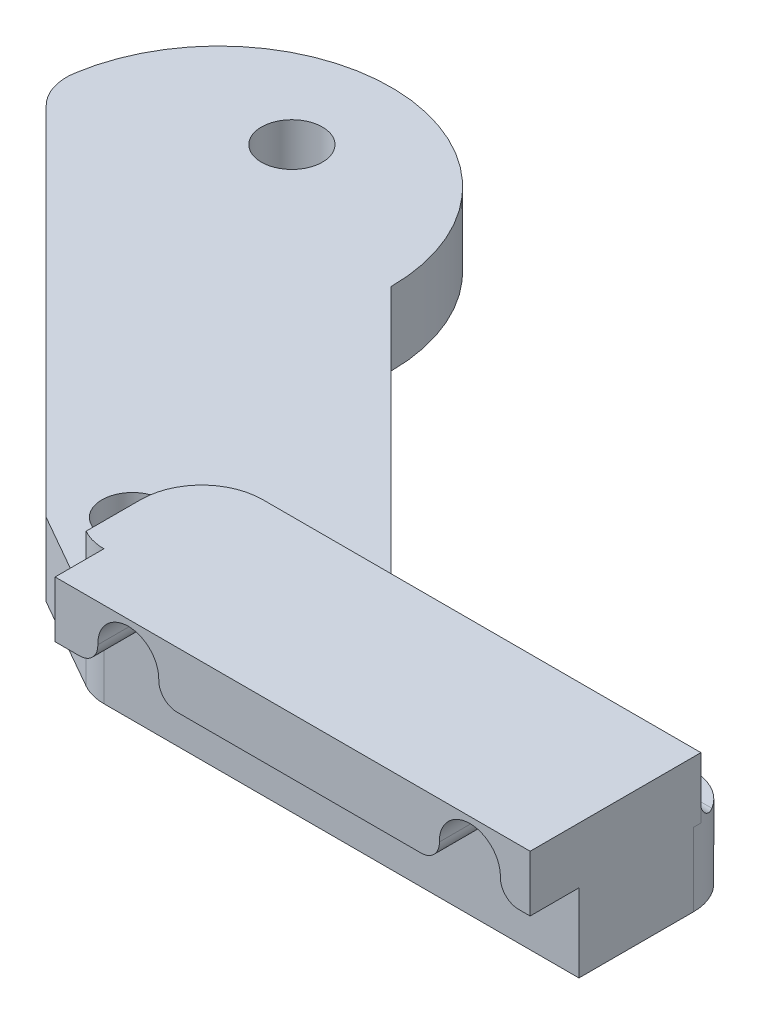
SolidWorks part; units mm, degrees
ref_plane "Front Plane" through (0, 0, 0) normal (0, 0, 1) x (1, 0, 0)
ref_plane "Top Plane" through (0, 0, 0) normal (0, 1, 0) x (1, 0, 0)
ref_plane "Right Plane" through (0, 0, 0) normal (1, 0, 0) x (0, 0, -1)
sketch "Sketch1" plane through (0, 0, 0) normal (0, 1, 0) x (1, 0, 0)
  line L0 (0, 6.35) -> (12.3665, 6.35)
  line L1 (12.3665, 6.35) -> (57.15, 6.35)
  line L2 (6.35, 0) -> (6.35, -10.668)
  line L3 (6.35, -10.668) -> (57.15, -10.668)
  line L4 (57.15, 6.35) -> (57.15, -10.668)
  line L5 (20.5908, 6.35) -> (-7.3492, 34.29)
  line L6 (-4.4901, -4.4901) -> (-43.2703, 34.29)
  line L7 (-4.4901, -4.4901) -> (6.35, -10.668)
  circle A0 centre (0, 0) radius 3.175
  arc A1 (0, 6.35) -> (6.35, 0) centre (0, 0) ccw
  arc A2 (-43.2703, 34.29) -> (-7.3492, 34.29) centre (-25.3097, 34.29) cw
  point P13 (-4.4901, -4.4901)
  dimension "D1" = 12.7
  dimension "D2" = 6.35
  dimension "D3" = 6.35
  dimension "D4" = 50.8
  dimension "D5" = 17.018
  dimension "D6" = 45
  dimension "D7" = 25.4
  dimension "D8" = 27.94
extrude "Boss-Extrude1" add sketch "Sketch1" along normal mid plane 7.62 contours A2 L6 A1 L0 L1 L5 | L0 A1 L2 L3 L4 L1 A0 | A1 L7 L2 region at (-15.7867, 0, -26.7963) region at (28.4111, 0, 1.8819) region at (4.1931, 0, 6.7992)
fillet "Fillet1" radius 5.08 4 edges at (57.15, 0, -6.35) (20.5908, 0, -6.35) (6.35, 0, 10.668) (-43.2703, 0, -34.29)
sketch "Sketch3" plane through (0, 3.81, 0) normal (0, 1, 0) x (1, 0, 0)
  circle A0 centre (-25.3097, 41.91) radius 3.175
  arc A1 (-7.3492, 34.29) -> (-43.0622, 37.016) centre (-25.3097, 34.29) ccw construction
  arc A2 (-7.3492, 34.29) -> (-43.0622, 37.016) centre (-25.3097, 34.29) ccw
  dimension "D2" = 6.35
  dimension "D1" = 7.62
extrude "Cut-Extrude2" cut sketch "Sketch3" against normal through all contours A0 region at (-25.3097, 3.81, -41.91)
sketch "Sketch4" plane through (0, 3.81, 0) normal (0, 1, 0) x (1, 0, 0)
  line L1 (57.15, -10.668) -> (7.6959, -10.668)
  line L2 (57.15, -10.668) -> (57.15, 2.032)
  line L3 (57.15, 2.032) -> (11.5306, 2.032)
  line L4 (5.1806, -10.0016) -> (5.1806, -4.318)
  arc A0 (5.1806, -10.0016) -> (7.6959, -10.668) centre (7.6959, -5.588) ccw construction
  arc A1 (5.1806, -10.0016) -> (7.6959, -10.668) centre (7.6959, -5.588) ccw
  arc A2 (11.5306, 2.032) -> (5.1806, -4.318) centre (11.5306, -4.318) ccw
  dimension "D2" = 6.35
  dimension "D1" = 12.7
extrude "Boss-Extrude2" add sketch "Sketch4" along normal blind 6.35
sketch "Sketch6" plane through (0, 0, 10.668) normal (0, 0, 1) x (1, 0, 0)
  line L0 (7.6959, 10.16) -> (7.6959, -3.81) construction
  line L1 (7.6959, 10.16) -> (57.15, 10.16) construction
  circle A0 centre (15.3159, 6.35) radius 2.286
  circle A1 centre (50.8759, 6.35) radius 2.286
  dimension "D1" = 4.572
  dimension "D2" = 4.572
  dimension "D3" = 35.56
  dimension "D4" = 7.62
  dimension "D5" = 3.81
extrude "Cut-Extrude3" cut sketch "Sketch6" against normal blind 6.35
sketch "Sketch7" plane through (0, 0, 10.668) normal (0, 0, 1) x (1, 0, 0)
  line L0 (57.15, 10.16) -> (57.15, -3.81) construction
  line L1 (7.6959, 10.16) -> (57.15, 10.16)
  line L2 (7.6959, 10.16) -> (7.6959, 4.318)
  line L3 (7.6959, 4.318) -> (57.15, 4.318)
  line L4 (57.15, 10.16) -> (57.15, 4.318)
  circle A4 centre (15.3159, 6.35) radius 3.175
  circle A5 centre (50.8759, 6.35) radius 3.175
  circle M3 centre (15.3159, 6.35) radius 2.286
  circle M4 centre (50.8759, 6.35) radius 2.286
  line M5 (57.15, -3.81) -> (57.15, 10.16)
  line M6 (57.15, 10.16) -> (7.6959, 10.16)
  line M7 (7.6959, 10.16) -> (7.6959, -3.81)
  dimension "D2" = 6.35
  dimension "D3" = 6.35
  dimension "D1" = 5.842
extrude "Boss-Extrude3" add sketch "Sketch7" along normal blind 5.08 contours L3 M7 M3 M4 M5 M6 region at (32.2626, 7.3678, 10.668)
fillet "Fillet2" radius 1.905 4 edges at (53.3155, 4.318, 13.208) (48.4364, 4.318, 13.208) (17.7555, 4.318, 13.208) (12.8764, 4.318, 13.208)
fillet "Fillet3" radius 1.905 3 edges at (5.1806, 3.81, 7.1598) (7.0405, 3.81, -0.1721) (34.3116, 3.81, -2.032)
